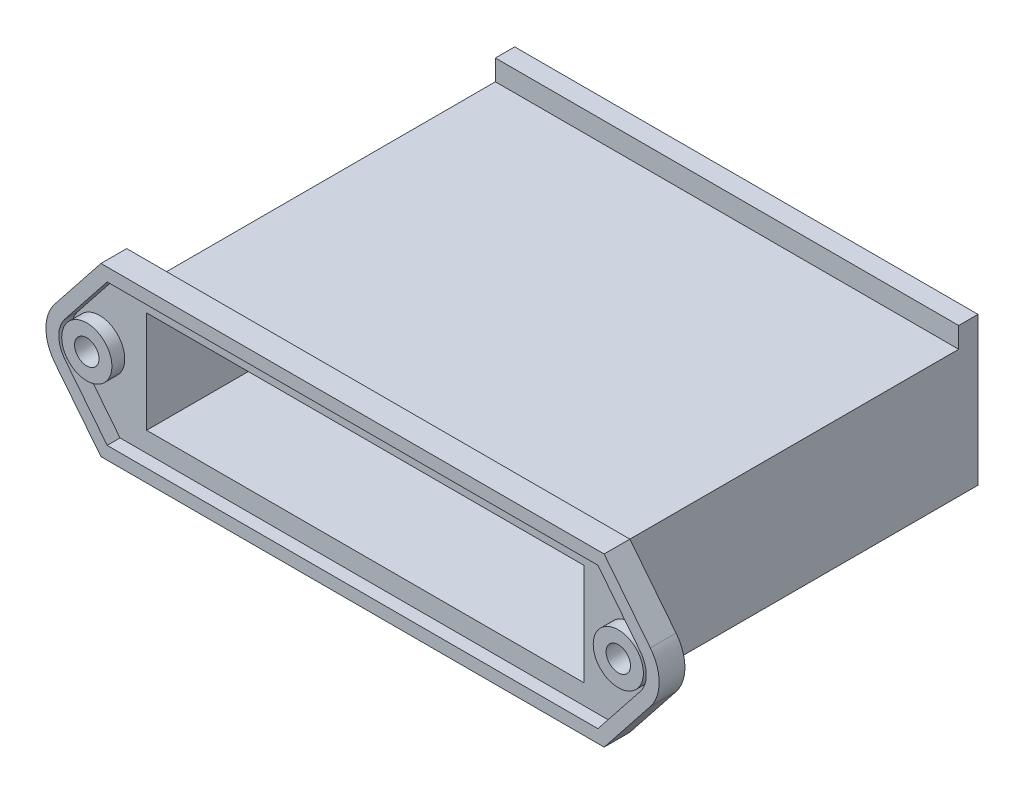
SolidWorks part; units mm, degrees
ref_plane "Front Plane" through (0, 0, 0) normal (0, 0, 1) x (1, 0, 0)
ref_plane "Top Plane" through (0, 0, 0) normal (0, 1, 0) x (1, 0, 0)
ref_plane "Right Plane" through (0, 0, 0) normal (1, 0, 0) x (0, 0, -1)
sketch "Sketch1" plane through (0, 0, 0) normal (0, 1, 0) x (1, 0, 0)
  line L0 (0, 28.6) -> (0, 0) construction
  line L1 (-36, 28.6) -> (36, 28.6)
  line L2 (-36, 28.6) -> (-36, -28.6)
  line L3 (-36, -28.6) -> (36, -28.6)
  line L4 (36, 28.6) -> (36, -28.6)
  line L5 (0, 0) -> (0, -28.6) construction
  dimension "D1" = 57.2
  dimension "D2" = 72
extrude "Boss-Extrude1" add sketch "Sketch1" along normal mid plane 19.8
sketch "Sketch2" plane through (0, 0, 28.6) normal (0, 0, 1) x (1, 0, 0)
  line L0 (0, 13) -> (0, 0) construction
  line L1 (-39.1, 13) -> (39.1, 13)
  line L2 (-39.1, 13) -> (-39.1, -13) construction
  line L3 (-39.1, -13) -> (39.1, -13)
  line L4 (39.1, 13) -> (39.1, -13) construction
  line L5 (0, 0) -> (0, -13) construction
  line L6 (-41.3, 0) -> (0, 0) construction
  line L7 (0, 0) -> (41.3, 0) construction
  line L8 (-46.2767, 3.9439) -> (-39.1, 13)
  line L9 (39.1, 13) -> (46.2767, 3.9439)
  line L10 (46.2767, -3.9439) -> (39.1, -13)
  line L11 (-46.2767, -3.9439) -> (-39.1, -13)
  line L12 (-47.65, 0) -> (-41.3, 0) construction
  line L13 (47.65, 0) -> (41.3, 0) construction
  line L14 (-36, 9.9) -> (-36, 13) construction
  line L15 (-36, 9.9) -> (-39.1, 9.9) construction
  circle A0 centre (-41.3, 0) radius 1.9
  circle A1 centre (41.3, 0) radius 1.9
  arc A2 (-46.2767, -3.9439) -> (-46.2767, 3.9439) centre (-41.3, 0) cw
  arc A3 (46.2767, 3.9439) -> (46.2767, -3.9439) centre (41.3, 0) cw
  dimension "D2" = 3.8
  dimension "D1" = 26
  dimension "D3" = 95.3
  dimension "D4" = 82.6
extrude "Boss-Extrude2" add sketch "Sketch2" along normal blind 4
sketch "Sketch4" plane through (0, 0, -28.6) normal (0, 0, -1) x (-1, 0, 0)
  line L0 (36, 9.9) -> (36, -9.9) construction
  line L1 (-36, -9.9) -> (36, -9.9)
  line L2 (-36, -9.9) -> (-36, 13.1)
  line L3 (-36, 13.1) -> (36, 13.1)
  line L4 (36, -9.9) -> (36, 13.1)
  dimension "D1" = 23
extrude "Boss-Extrude3" add sketch "Sketch4" against normal blind 3
shell "Shell1" thickness 2 removed face at (0, 0, 32.6)
